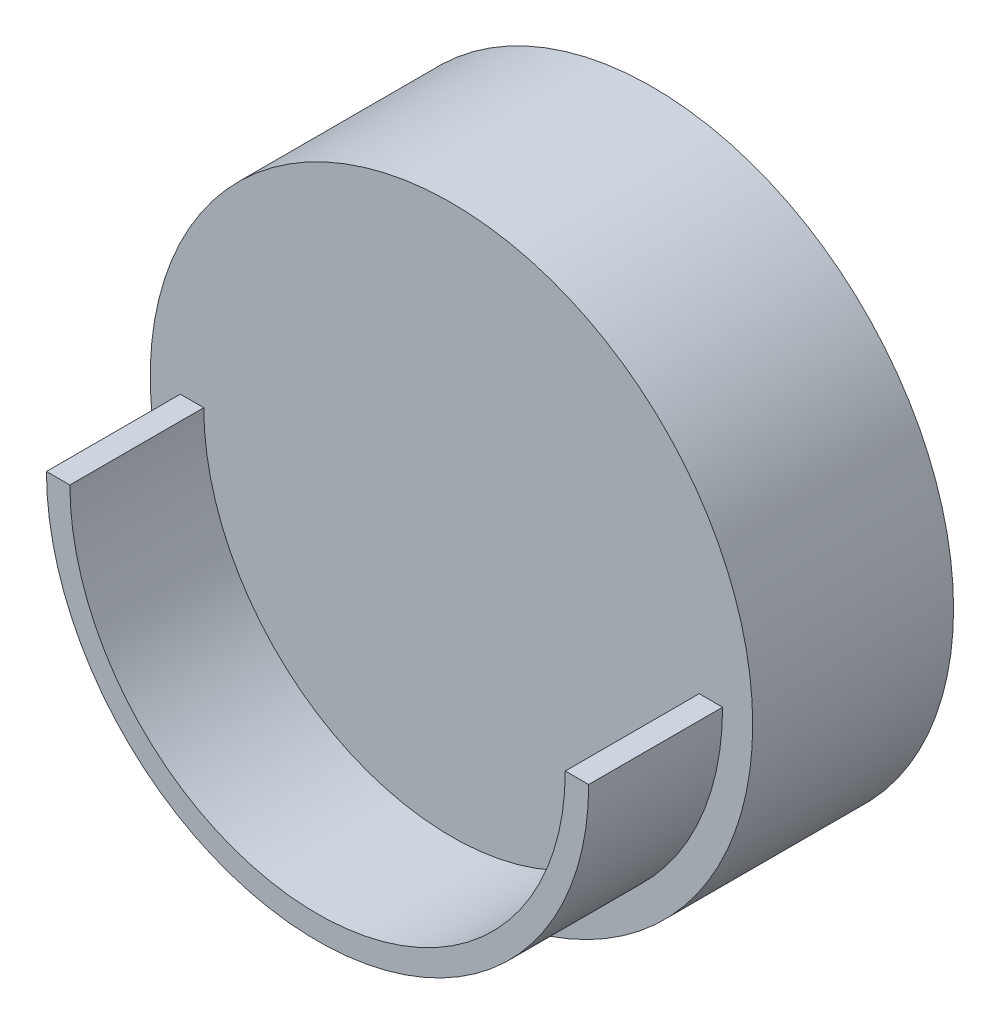
SolidWorks part; units mm, degrees
ref_plane "Front Plane" through (0, 0, 0) normal (0, 0, 1) x (1, 0, 0)
ref_plane "Top Plane" through (0, 0, 0) normal (0, 1, 0) x (1, 0, 0)
ref_plane "Right Plane" through (0, 0, 0) normal (1, 0, 0) x (0, 0, -1)
sketch "Sketch1" plane through (0, 0, 0) normal (0, 0, 1) x (1, 0, 0)
  circle A0 centre (0, 0) radius 22.5
  dimension "D1" = 45
extrude "Boss-Extrude1" add sketch "Sketch1" along normal blind 15
sketch "Sketch2" plane through (0, 0, 15) normal (0, 0, 1) x (1, 0, 0)
  circle A0 centre (0, 0) radius 20.25
  circle A1 centre (0, 0) radius 18.5
  dimension "D1" = 40.5
  dimension "D2" = 37
extrude "Boss-Extrude2" add sketch "Sketch2" along normal blind 10
sketch "Sketch3" plane through (0, 0, 15) normal (0, 0, 1) x (1, 0, 0)
  line L0 (0, 22.5) -> (0.5437, 23.9938)
  line L2 (2.3519, 22.3767) -> (1.9673, 23.9192)
  line L3 (0, 0) -> (0, 22.5)
  line L4 (2.3519, 22.3767) -> (0, 0)
  line L5 (0.5437, 23.9938) -> (1.9673, 23.9192)
  line L6 (0, 22.5) -> (0.5437, 23.9938)
  line L7 (1.9673, 23.9192) -> (2.3519, 22.3767)
  line L8 (3.1314, 22.281) -> (3.8777, 23.6847)
  line L9 (3.8777, 23.6847) -> (5.2771, 23.4127)
  line L10 (5.4432, 21.8317) -> (5.2771, 23.4127)
  line L11 (6.2018, 21.6284) -> (7.1362, 22.9145)
  line L12 (7.1362, 22.9145) -> (8.4841, 22.4504)
  line L13 (8.4286, 20.8616) -> (8.4841, 22.4504)
  line L14 (9.1516, 20.5548) -> (10.2559, 21.6983)
  line L15 (10.2559, 21.6983) -> (11.5261, 21.0511)
  line L16 (11.25, 19.4856) -> (11.5261, 21.0511)
  line L17 (11.9232, 19.0811) -> (13.1759, 20.0598)
  line L18 (13.1759, 20.0598) -> (14.3436, 19.2421)
  line L19 (13.8524, 17.7302) -> (14.3436, 19.2421)
  line L20 (14.4627, 17.236) -> (15.8395, 18.0309)
  line L21 (15.8395, 18.0309) -> (16.882, 17.0586)
  line L22 (16.1851, 15.6298) -> (16.882, 17.0586)
  line L23 (16.7208, 15.0554) -> (18.1947, 15.651)
  line L24 (18.1947, 15.651) -> (19.0918, 14.5431)
  line L25 (18.2029, 13.2252) -> (19.0918, 14.5431)
  line L26 (18.6533, 12.5818) -> (20.1958, 12.9664)
  line L27 (20.1958, 12.9664) -> (20.93, 11.7445)
  line L28 (19.8663, 10.5631) -> (20.93, 11.7445)
  line L29 (20.2229, 9.8634) -> (21.8039, 10.0295)
  line L30 (21.8039, 10.0295) -> (22.3609, 8.7173)
  line L31 (21.1431, 7.6955) -> (22.3609, 8.7173)
  line L32 (21.3988, 6.9529) -> (22.9875, 6.8974)
  line L33 (22.9875, 6.8974) -> (23.3565, 5.5204)
  line L34 (22.0083, 4.678) -> (23.3565, 5.5204)
  line L35 (22.1582, 3.9071) -> (23.7237, 3.631)
  line L36 (23.7237, 3.631) -> (23.8975, 2.2161)
  line L37 (22.4452, 1.5695) -> (23.8975, 2.2161)
  line L38 (22.4863, 0.7852) -> (23.9982, 0.294)
  line L39 (23.9982, 0.294) -> (23.9733, -1.1313)
  line L40 (22.4452, -1.5695) -> (23.9733, -1.1313)
  line L41 (22.3767, -2.3519) -> (23.8056, -3.0488)
  line L42 (23.8056, -3.0488) -> (23.5826, -4.4568)
  line L43 (22.0083, -4.678) -> (23.5826, -4.4568)
  line L44 (21.8317, -5.4432) -> (23.1496, -6.3322)
  line L45 (23.1496, -6.3322) -> (22.7328, -7.6955)
  line L46 (21.1431, -7.6955) -> (22.7328, -7.6955)
  line L47 (20.8616, -8.4286) -> (22.043, -9.4924)
  line L48 (22.043, -9.4924) -> (21.4406, -10.7844)
  line L49 (19.8663, -10.5631) -> (21.4406, -10.7844)
  line L50 (19.4856, -11.25) -> (20.5074, -12.4678)
  line L51 (20.5074, -12.4678) -> (19.731, -13.6634)
  line L52 (18.2029, -13.2252) -> (19.731, -13.6634)
  line L53 (17.7302, -13.8524) -> (18.5727, -15.2005)
  line L54 (18.5727, -15.2005) -> (17.6374, -16.2764)
  line L55 (16.1851, -15.6298) -> (17.6374, -16.2764)
  line L56 (15.6298, -16.1851) -> (16.2764, -17.6374)
  line L57 (16.2764, -17.6374) -> (15.2005, -18.5727)
  line L58 (13.8524, -17.7302) -> (15.2005, -18.5727)
  line L59 (13.2252, -18.2029) -> (13.6634, -19.731)
  line L60 (13.6634, -19.731) -> (12.4678, -20.5074)
  line L61 (11.25, -19.4856) -> (12.4678, -20.5074)
  line L62 (10.5631, -19.8663) -> (10.7844, -21.4406)
  line L63 (10.7844, -21.4406) -> (9.4924, -22.043)
  line L64 (8.4286, -20.8616) -> (9.4924, -22.043)
  line L65 (7.6955, -21.1431) -> (7.6955, -22.7328)
  line L66 (7.6955, -22.7328) -> (6.3322, -23.1496)
  line L67 (5.4432, -21.8317) -> (6.3322, -23.1496)
  line L68 (4.678, -22.0083) -> (4.4568, -23.5826)
  line L69 (4.4568, -23.5826) -> (3.0488, -23.8056)
  line L70 (2.3519, -22.3767) -> (3.0488, -23.8056)
  line L71 (1.5695, -22.4452) -> (1.1313, -23.9733)
  line L72 (1.1313, -23.9733) -> (-0.294, -23.9982)
  line L73 (-0.7852, -22.4863) -> (-0.294, -23.9982)
  line L74 (-1.5695, -22.4452) -> (-2.2161, -23.8975)
  line L75 (-2.2161, -23.8975) -> (-3.631, -23.7237)
  line L76 (-3.9071, -22.1582) -> (-3.631, -23.7237)
  line L77 (-4.678, -22.0083) -> (-5.5204, -23.3565)
  line L78 (-5.5204, -23.3565) -> (-6.8974, -22.9875)
  line L79 (-6.9529, -21.3988) -> (-6.8974, -22.9875)
  line L80 (-7.6955, -21.1431) -> (-8.7173, -22.3609)
  line L81 (-8.7173, -22.3609) -> (-10.0295, -21.8039)
  line L82 (-9.8634, -20.2229) -> (-10.0295, -21.8039)
  line L83 (-10.5631, -19.8663) -> (-11.7445, -20.93)
  line L84 (-11.7445, -20.93) -> (-12.9664, -20.1958)
  line L85 (-12.5818, -18.6533) -> (-12.9664, -20.1958)
  line L86 (-13.2252, -18.2029) -> (-14.5431, -19.0918)
  line L87 (-14.5431, -19.0918) -> (-15.651, -18.1947)
  line L88 (-15.0554, -16.7208) -> (-15.651, -18.1947)
  line L89 (-15.6298, -16.1851) -> (-17.0586, -16.882)
  line L90 (-17.0586, -16.882) -> (-18.0309, -15.8395)
  line L91 (-17.236, -14.4627) -> (-18.0309, -15.8395)
  line L92 (-17.7302, -13.8524) -> (-19.2421, -14.3436)
  line L93 (-19.2421, -14.3436) -> (-20.0598, -13.1759)
  line L94 (-19.0811, -11.9232) -> (-20.0598, -13.1759)
  line L95 (-19.4856, -11.25) -> (-21.0511, -11.5261)
  line L96 (-21.0511, -11.5261) -> (-21.6983, -10.2559)
  line L97 (-20.5548, -9.1516) -> (-21.6983, -10.2559)
  line L98 (-20.8616, -8.4286) -> (-22.4504, -8.4841)
  line L99 (-22.4504, -8.4841) -> (-22.9145, -7.1362)
  line L100 (-21.6284, -6.2018) -> (-22.9145, -7.1362)
  line L101 (-21.8317, -5.4432) -> (-23.4127, -5.2771)
  line L102 (-23.4127, -5.2771) -> (-23.6847, -3.8777)
  line L103 (-22.281, -3.1314) -> (-23.6847, -3.8777)
  line L104 (-22.3767, -2.3519) -> (-23.9192, -1.9673)
  line L105 (-23.9192, -1.9673) -> (-23.9938, -0.5437)
  line L106 (-22.5, 0) -> (-23.9938, -0.5437)
  line L107 (-22.4863, 0.7852) -> (-23.9602, 1.3808)
  line L108 (-23.9602, 1.3808) -> (-23.836, 2.8009)
  line L109 (-22.281, 3.1314) -> (-23.836, 2.8009)
  line L110 (-22.1582, 3.9071) -> (-23.5349, 4.7019)
  line L111 (-23.5349, 4.7019) -> (-23.2142, 6.0909)
  line L112 (-21.6284, 6.2018) -> (-23.2142, 6.0909)
  line L113 (-21.3988, 6.9529) -> (-22.6515, 7.9316)
  line L114 (-22.6515, 7.9316) -> (-22.1406, 9.2625)
  line L115 (-20.5548, 9.1516) -> (-22.1406, 9.2625)
  line L116 (-20.2229, 9.8634) -> (-21.3272, 11.0069)
  line L117 (-21.3272, 11.0069) -> (-20.6361, 12.2537)
  line L118 (-19.0811, 11.9232) -> (-20.6361, 12.2537)
  line L119 (-18.6533, 12.5818) -> (-19.5878, 13.8679)
  line L120 (-19.5878, 13.8679) -> (-18.7298, 15.0064)
  line L121 (-17.236, 14.4627) -> (-18.7298, 15.0064)
  line L122 (-16.7208, 15.0554) -> (-17.4671, 16.4591)
  line L123 (-17.4671, 16.4591) -> (-16.4591, 17.4671)
  line L124 (-15.0554, 16.7208) -> (-16.4591, 17.4671)
  line L125 (-14.4627, 17.236) -> (-15.0064, 18.7298)
  line L126 (-15.0064, 18.7298) -> (-13.8679, 19.5878)
  line L127 (-12.5818, 18.6533) -> (-13.8679, 19.5878)
  line L128 (-11.9232, 19.0811) -> (-12.2537, 20.6361)
  line L129 (-12.2537, 20.6361) -> (-11.0069, 21.3272)
  line L130 (-9.8634, 20.2229) -> (-11.0069, 21.3272)
  line L131 (-9.1516, 20.5548) -> (-9.2625, 22.1406)
  line L132 (-9.2625, 22.1406) -> (-7.9316, 22.6515)
  line L133 (-6.9529, 21.3988) -> (-7.9316, 22.6515)
  line L134 (-6.2018, 21.6284) -> (-6.0909, 23.2142)
  line L135 (-6.0909, 23.2142) -> (-4.7019, 23.5349)
  line L136 (-3.9071, 22.1582) -> (-4.7019, 23.5349)
  line L137 (-3.1314, 22.281) -> (-2.8009, 23.836)
  line L138 (-2.8009, 23.836) -> (-1.3808, 23.9602)
  line L139 (-0.7852, 22.4863) -> (-1.3808, 23.9602)
  arc A0 (0, 22.5) -> (2.3519, 22.3767) centre (0, 0) cw
  circle A1 centre (0, 0) radius 22.5 construction
  circle A2 centre (0, 0) radius 18.5 construction
  arc A4 (0.5437, 23.9938) -> (1.9673, 23.9192) centre (1.2243, 23.3613) cw
  arc A5 (0, 22.5) -> (2.3519, 22.3767) centre (0, 0) cw
  arc A6 (3.1314, 22.281) -> (5.4432, 21.8317) centre (0, 0) cw
  arc A7 (3.8777, 23.6847) -> (5.2771, 23.4127) centre (4.4637, 22.9636) cw
  arc A8 (6.2018, 21.6284) -> (8.4286, 20.8616) centre (0, 0) cw
  arc A9 (7.1362, 22.9145) -> (8.4841, 22.4504) centre (7.6161, 22.1189) cw
  arc A10 (9.1516, 20.5548) -> (11.25, 19.4856) centre (0, 0) cw
  arc A11 (10.2559, 21.6983) -> (11.5261, 21.0511) centre (10.6204, 20.8437) cw
  arc A12 (11.9232, 19.0811) -> (13.8524, 17.7302) centre (0, 0) cw
  arc A13 (13.1759, 20.0598) -> (14.3436, 19.2421) centre (13.4179, 19.1628) cw
  arc A14 (14.4627, 17.236) -> (16.1851, 15.6298) centre (0, 0) cw
  arc A15 (15.8395, 18.0309) -> (16.882, 17.0586) centre (15.9543, 17.1089) cw
  arc A16 (16.7208, 15.0554) -> (18.2029, 13.2252) centre (0, 0) cw
  arc A17 (18.1947, 15.651) -> (19.0918, 14.5431) centre (18.1801, 14.7219) cw
  arc A18 (18.6533, 12.5818) -> (19.8663, 10.5631) centre (0, 0) cw
  arc A19 (20.1958, 12.9664) -> (20.93, 11.7445) centre (20.0521, 12.0485) cw
  arc A20 (20.2229, 9.8634) -> (21.1431, 7.6955) centre (0, 0) cw
  arc A21 (21.8039, 10.0295) -> (22.3609, 8.7173) centre (21.5337, 9.1405) cw
  arc A22 (21.3988, 6.9529) -> (22.0083, 4.678) centre (0, 0) cw
  arc A23 (22.9875, 6.8974) -> (23.3565, 5.5204) centre (22.5963, 6.0547) cw
  arc A24 (22.1582, 3.9071) -> (22.4452, 1.5695) centre (0, 0) cw
  arc A25 (23.7237, 3.631) -> (23.8975, 2.2161) centre (23.219, 2.8509) cw
  arc A26 (22.4863, 0.7852) -> (22.4452, -1.5695) centre (0, 0) cw
  arc A27 (23.9982, 0.294) -> (23.9733, -1.1313) centre (23.3898, -0.4083) cw
  arc A28 (22.3767, -2.3519) -> (22.0083, -4.678) centre (0, 0) cw
  arc A29 (23.8056, -3.0488) -> (23.5826, -4.4568) centre (23.1054, -3.6595) cw
  arc A30 (21.8317, -5.4432) -> (21.1431, -7.6955) centre (0, 0) cw
  arc A31 (23.1496, -6.3322) -> (22.7328, -7.6955) centre (22.3712, -6.8396) cw
  arc A32 (20.8616, -8.4286) -> (19.8663, -10.5631) centre (0, 0) cw
  arc A33 (22.043, -9.4924) -> (21.4406, -10.7844) centre (21.2016, -9.8865) cw
  arc A34 (19.4856, -11.25) -> (18.2029, -13.2252) centre (0, 0) cw
  arc A35 (20.5074, -12.4678) -> (19.731, -13.6634) centre (19.6194, -12.741) cw
  arc A36 (17.7302, -13.8524) -> (16.1851, -15.6298) centre (0, 0) cw
  arc A37 (18.5727, -15.2005) -> (17.6374, -16.2764) centre (17.6552, -15.3475) cw
  arc A38 (15.6298, -16.1851) -> (13.8524, -17.7302) centre (0, 0) cw
  arc A39 (16.2764, -17.6374) -> (15.2005, -18.5727) centre (15.3475, -17.6552) cw
  arc A40 (13.2252, -18.2029) -> (11.25, -19.4856) centre (0, 0) cw
  arc A41 (13.6634, -19.731) -> (12.4678, -20.5074) centre (12.741, -19.6194) cw
  arc A42 (10.5631, -19.8663) -> (8.4286, -20.8616) centre (0, 0) cw
  arc A43 (10.7844, -21.4406) -> (9.4924, -22.043) centre (9.8865, -21.2016) cw
  arc A44 (7.6955, -21.1431) -> (5.4432, -21.8317) centre (0, 0) cw
  arc A45 (7.6955, -22.7328) -> (6.3322, -23.1496) centre (6.8396, -22.3712) cw
  arc A46 (4.678, -22.0083) -> (2.3519, -22.3767) centre (0, 0) cw
  arc A47 (4.4568, -23.5826) -> (3.0488, -23.8056) centre (3.6595, -23.1054) cw
  arc A48 (1.5695, -22.4452) -> (-0.7852, -22.4863) centre (0, 0) cw
  arc A49 (1.1313, -23.9733) -> (-0.294, -23.9982) centre (0.4083, -23.3898) cw
  arc A50 (-1.5695, -22.4452) -> (-3.9071, -22.1582) centre (0, 0) cw
  arc A51 (-2.2161, -23.8975) -> (-3.631, -23.7237) centre (-2.8509, -23.219) cw
  arc A52 (-4.678, -22.0083) -> (-6.9529, -21.3988) centre (0, 0) cw
  arc A53 (-5.5204, -23.3565) -> (-6.8974, -22.9875) centre (-6.0547, -22.5963) cw
  arc A54 (-7.6955, -21.1431) -> (-9.8634, -20.2229) centre (0, 0) cw
  arc A55 (-8.7173, -22.3609) -> (-10.0295, -21.8039) centre (-9.1405, -21.5337) cw
  arc A56 (-10.5631, -19.8663) -> (-12.5818, -18.6533) centre (0, 0) cw
  arc A57 (-11.7445, -20.93) -> (-12.9664, -20.1958) centre (-12.0485, -20.0521) cw
  arc A58 (-13.2252, -18.2029) -> (-15.0554, -16.7208) centre (0, 0) cw
  arc A59 (-14.5431, -19.0918) -> (-15.651, -18.1947) centre (-14.7219, -18.1801) cw
  arc A60 (-15.6298, -16.1851) -> (-17.236, -14.4627) centre (0, 0) cw
  arc A61 (-17.0586, -16.882) -> (-18.0309, -15.8395) centre (-17.1089, -15.9543) cw
  arc A62 (-17.7302, -13.8524) -> (-19.0811, -11.9232) centre (0, 0) cw
  arc A63 (-19.2421, -14.3436) -> (-20.0598, -13.1759) centre (-19.1628, -13.4179) cw
  arc A64 (-19.4856, -11.25) -> (-20.5548, -9.1516) centre (0, 0) cw
  arc A65 (-21.0511, -11.5261) -> (-21.6983, -10.2559) centre (-20.8437, -10.6204) cw
  arc A66 (-20.8616, -8.4286) -> (-21.6284, -6.2018) centre (0, 0) cw
  arc A67 (-22.4504, -8.4841) -> (-22.9145, -7.1362) centre (-22.1189, -7.6161) cw
  arc A68 (-21.8317, -5.4432) -> (-22.281, -3.1314) centre (0, 0) cw
  arc A69 (-23.4127, -5.2771) -> (-23.6847, -3.8777) centre (-22.9636, -4.4637) cw
  arc A70 (-22.3767, -2.3519) -> (-22.5, 0) centre (0, 0) cw
  arc A71 (-23.9192, -1.9673) -> (-23.9938, -0.5437) centre (-23.3613, -1.2243) cw
  arc A72 (-22.4863, 0.7852) -> (-22.281, 3.1314) centre (0, 0) cw
  arc A73 (-23.9602, 1.3808) -> (-23.836, 2.8009) centre (-23.3044, 2.0389) cw
  arc A74 (-22.1582, 3.9071) -> (-21.6284, 6.2018) centre (0, 0) cw
  arc A75 (-23.5349, 4.7019) -> (-23.2142, 6.0909) centre (-22.7938, 5.2624) cw
  arc A76 (-21.3988, 6.9529) -> (-20.5548, 9.1516) centre (0, 0) cw
  arc A77 (-22.6515, 7.9316) -> (-22.1406, 9.2625) centre (-21.8396, 8.3834) cw
  arc A78 (-20.2229, 9.8634) -> (-19.0811, 11.9232) centre (0, 0) cw
  arc A79 (-21.3272, 11.0069) -> (-20.6361, 12.2537) centre (-20.4603, 11.3413) cw
  arc A80 (-18.6533, 12.5818) -> (-17.236, 14.4627) centre (0, 0) cw
  arc A81 (-19.5878, 13.8679) -> (-18.7298, 15.0064) centre (-18.6828, 14.0785) cw
  arc A82 (-16.7208, 15.0554) -> (-15.0554, 16.7208) centre (0, 0) cw
  arc A83 (-17.4671, 16.4591) -> (-16.4591, 17.4671) centre (-16.5416, 16.5416) cw
  arc A84 (-14.4627, 17.236) -> (-12.5818, 18.6533) centre (0, 0) cw
  arc A85 (-15.0064, 18.7298) -> (-13.8679, 19.5878) centre (-14.0785, 18.6828) cw
  arc A86 (-11.9232, 19.0811) -> (-9.8634, 20.2229) centre (0, 0) cw
  arc A87 (-12.2537, 20.6361) -> (-11.0069, 21.3272) centre (-11.3413, 20.4603) cw
  arc A88 (-9.1516, 20.5548) -> (-6.9529, 21.3988) centre (0, 0) cw
  arc A89 (-9.2625, 22.1406) -> (-7.9316, 22.6515) centre (-8.3834, 21.8396) cw
  arc A90 (-6.2018, 21.6284) -> (-3.9071, 22.1582) centre (0, 0) cw
  arc A91 (-6.0909, 23.2142) -> (-4.7019, 23.5349) centre (-5.2624, 22.7938) cw
  arc A92 (-3.1314, 22.281) -> (-0.7852, 22.4863) centre (0, 0) cw
  arc A93 (-2.8009, 23.836) -> (-1.3808, 23.9602) centre (-2.0389, 23.3044) cw
  point P11 (0, 0)
  point P234 (0, 0)
  dimension "D1" = 20
  dimension "D4" = 45
  dimension "D2" = 6
  dimension "D3" = 160
sketch "Sketch4" plane through (0, 0, 0) normal (1, 0, 0) x (0, 0, -1)
  line L0 (-25, 20.25) -> (-25, -20.25) construction
  line L1 (-25, 0) -> (-15, 0)
  line L2 (-25, 0) -> (-25, 24.7521)
  line L3 (-25, 24.7521) -> (-15, 24.7521)
  line L4 (-15, 0) -> (-15, 24.7521)
  point P7 (-25, 20.0919)
  point P8 (-25, 20.0919)
extrude "Cut-Extrude1" cut sketch "Sketch4" against normal through all both and the other way through all
